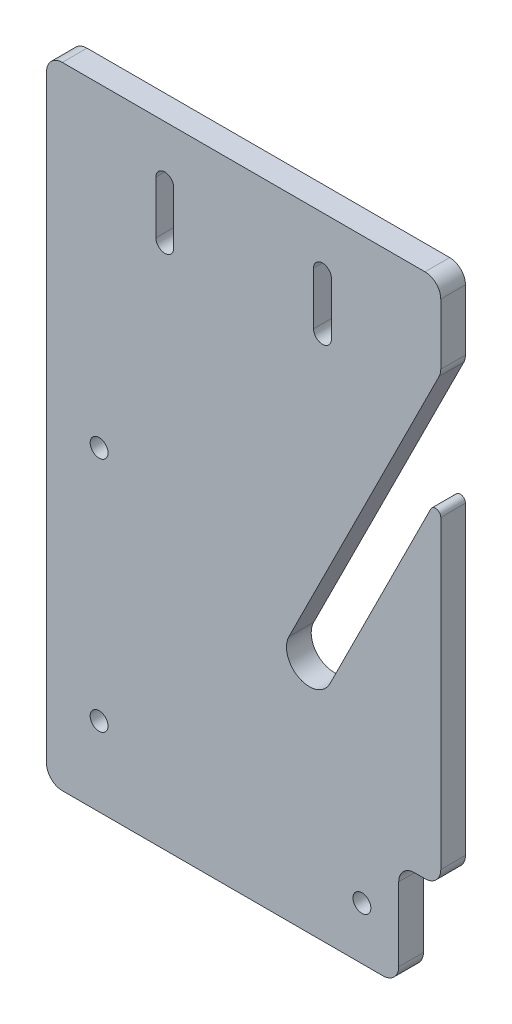
SolidWorks part; units mm, degrees
material "Acrylic (Medium-high impact)"
ref_plane "Front Plane" through (0, 0, 0) normal (0, 0, 1) x (1, 0, 0)
ref_plane "Top Plane" through (0, 0, 0) normal (0, 1, 0) x (1, 0, 0)
ref_plane "Right Plane" through (0, 0, 0) normal (1, 0, 0) x (0, 0, -1)
sketch "Sketch1" plane through (0, 0, 0) normal (0, 0, 1) x (1, 0, 0)
  line L0 (0, 0) -> (0, -120)
  line L1 (0, -120) -> (75, -120)
  line L2 (75, -120) -> (75, 0)
  line L3 (75, 0) -> (0, 0)
  line L4 (56.1092, -53.0546) -> (46.1092, -73.0546)
  line L5 (53.8908, -76.9454) -> (63.8908, -56.9454)
  line L6 (63.8908, -56.9454) -> (75, -34.7269)
  line L7 (56.1092, -53.0546) -> (75, -15.2731)
  circle A0 centre (50, -75) radius 4.35
  circle A1 centre (60, -110) radius 1.7
  circle A2 centre (10, -60) radius 1.7
  circle A3 centre (10, -105) radius 1.7
  circle A6 centre (60, -55) radius 4.35
  dimension "D4" = 8.7
  dimension "D6" = 3.4
  dimension "D8" = 3.4
  dimension "D9" = 3.4
  dimension "D10" = 15
  dimension "D16" = 8.7
  dimension "D1" = 120
  dimension "D2" = 75
  dimension "D3" = 50
  dimension "D5" = 45
  dimension "D7" = 10
  dimension "D12" = 15
  dimension "D13" = 10
  dimension "D15" = 45
  dimension "D17" = 10
  dimension "D18" = 20
extrude "Boss-Extrude1" add sketch "Sketch1" along normal blind 4.7 contours L2 L3 L0 L1 A6 L5 A0 L4 A3 A2 region at (36.0619, -60.432, 0)
fillet "Fillet1" radius 3 5 edges at (0, -120, 2.35) (75, -120, 2.35) (75, 0, 2.35) (0, 0, 2.35) (75, -15.2731, 2.35)
sketch "Sketch2" plane through (0, 0, 4.7) normal (0, 0, 1) x (1, 0, 0)
  line L0 (72, 0) -> (3, 0) construction
  line L1 (37.5, 0) -> (37.5, -120) construction
  line L2 (3, -120) -> (72, -120) construction
  line L3 (22.5, -10) -> (52.5, -10) construction
  line L4 (20.8, -10) -> (20.8, -20)
  line L5 (24.2, -10) -> (24.2, -20)
  line L6 (50.8, -10) -> (50.8, -20)
  line L7 (54.2, -10) -> (54.2, -20)
  arc A0 (24.2, -10) -> (20.8, -10) centre (22.5, -10) ccw
  arc A1 (54.2, -10) -> (50.8, -10) centre (52.5, -10) ccw
  arc A2 (20.8, -20) -> (24.2, -20) centre (22.5, -20) ccw
  arc A3 (50.8, -20) -> (54.2, -20) centre (52.5, -20) ccw
  point P10 (37.5, -10)
  dimension "D3" = 3.4
  dimension "D4" = 3.4
  dimension "D1" = 30
  dimension "D2" = 110
  dimension "D5" = 10
  dimension "D6" = 10
extrude "Cut-Extrude1" cut sketch "Sketch2" against normal through all
sketch "Sketch3" plane through (0, 0, 4.7) normal (0, 0, 1) x (1, 0, 0)
  line L0 (75, -117) -> (75, -34.7269) construction
  line L1 (75, -100) -> (67, -100)
  line L2 (75, -100) -> (75, -120)
  line L3 (75, -120) -> (67, -120)
  line L4 (67, -100) -> (67, -120)
  line L5 (3, -120) -> (72, -120) construction
  dimension "D1" = 8
  dimension "D2" = 20
extrude "Cut-Extrude2" cut sketch "Sketch3" against normal through all
fillet "Fillet2" radius 3 3 edges at (75, -100, 2.35) (67, -100, 2.35) (67, -120, 2.35)
fillet "Fillet3" radius 1 1 edges at (75, -34.7269, 2.35)
equation "\"D16@Sketch1\"=\"D4@Sketch1\""
